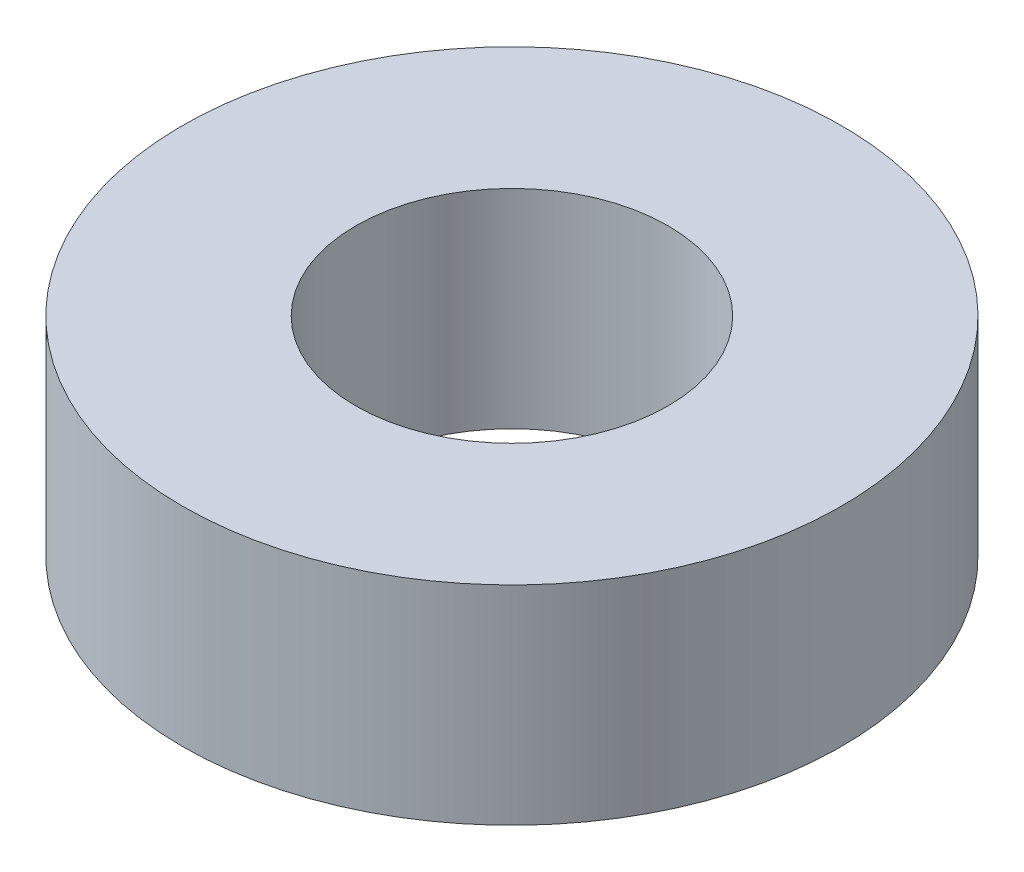
SolidWorks part; units mm, degrees
ref_plane "Front Plane" through (0, 0, 0) normal (0, 0, 1) x (1, 0, 0)
ref_plane "Top Plane" through (0, 0, 0) normal (0, 1, 0) x (1, 0, 0)
ref_plane "Right Plane" through (0, 0, 0) normal (1, 0, 0) x (0, 0, -1)
sketch "Sketch1" plane through (0, 0, 0) normal (0, 1, 0) x (1, 0, 0)
  circle A0 centre (0, 0) radius 47.5
  dimension "FLANGE_OD" = 95
extrude "Boss-Extrude1" add sketch "Sketch1" along normal blind 30
sketch "Sketch2" plane through (0, 0, 0) normal (0, 1, 0) x (1, 0, 0)
  circle A0 centre (0, 0) radius 22.5
  dimension "BORE_D" = 45
extrude "Cut-Extrude1" cut sketch "Sketch2" along normal through all
sketch "Sketch3" plane through (0, 30, 0) normal (0, 1, 0) x (1, 0, 0)
  circle A0 centre (0, 0) radius 14.6112 construction
  circle A1 centre (-14.6112, 0) radius 4.1905
  dimension "BOLT_D" = 8.381
  dimension "BOLT_PCD" = 29.2223
extrude "Cut-Extrude2" cut sketch "Sketch3" against normal blind 19.3445 rebuild error yes
pattern_circular "CirPattern1" count 3 over 360 rebuild error yes
